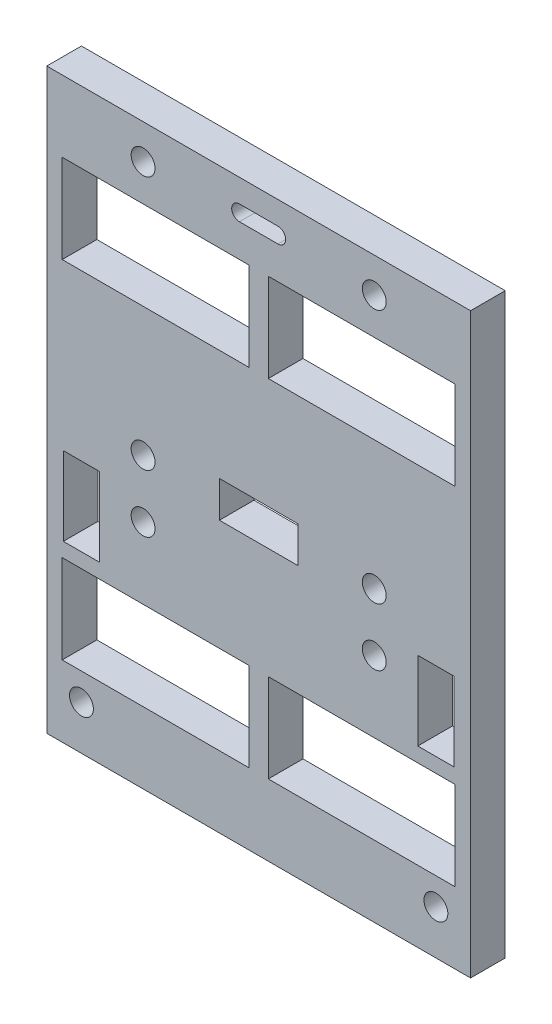
SolidWorks part; units mm, degrees
ref_plane "Front Plane" through (0, 0, 0) normal (0, 0, 1) x (1, 0, 0)
ref_plane "Top Plane" through (0, 0, 0) normal (0, 1, 0) x (1, 0, 0)
ref_plane "Right Plane" through (0, 0, 0) normal (1, 0, 0) x (0, 0, -1)
sketch "Sketch1" plane through (0, 0, 0) normal (0, 0, 1) x (1, 0, 0)
  line L0 (0, -37.5) -> (0, 37.5) construction
  line L1 (-27.5, -37.5) -> (27.5, -37.5)
  line L2 (-27.5, -37.5) -> (-27.5, 37.5)
  line L3 (-27.5, 37.5) -> (27.5, 37.5)
  line L4 (27.5, -37.5) -> (27.5, 37.5)
  line L5 (-27.5, -37.5) -> (27.5, 37.5) construction
  line L6 (-27.5, 37.5) -> (27.5, -37.5) construction
  line L7 (-27.5, 0) -> (27.5, 0) construction
  line L8 (-27.5, 22.5) -> (27.5, 22.5) construction
  line L9 (25.5, 16.75) -> (1.25, 28.25) construction
  line L10 (-25.5, 28.25) -> (-1.25, 28.25)
  line L11 (-25.5, 28.25) -> (-25.5, 16.75)
  line L12 (-25.5, 16.75) -> (-1.25, 16.75)
  line L13 (-1.25, 28.25) -> (-1.25, 16.75)
  line L14 (-25.5, 28.25) -> (-1.25, 16.75) construction
  line L15 (-25.5, 16.75) -> (-1.25, 28.25) construction
  line L16 (25.5, 28.25) -> (1.25, 16.75) construction
  line L17 (1.25, 28.25) -> (1.25, 16.75)
  line L18 (25.5, 16.75) -> (1.25, 16.75)
  line L19 (25.5, 28.25) -> (25.5, 16.75)
  line L20 (25.5, 28.25) -> (1.25, 28.25)
  line L21 (25.5, -28.25) -> (1.25, -16.75) construction
  line L22 (-25.5, -16.75) -> (-1.25, -28.25) construction
  line L23 (-25.5, -28.25) -> (-1.25, -16.75) construction
  line L24 (25.5, -16.75) -> (1.25, -28.25) construction
  line L25 (25.5, -28.25) -> (1.25, -28.25)
  line L26 (25.5, -28.25) -> (25.5, -16.75)
  line L27 (25.5, -16.75) -> (1.25, -16.75)
  line L28 (1.25, -28.25) -> (1.25, -16.75)
  line L29 (-1.25, -28.25) -> (-1.25, -16.75)
  line L30 (-25.5, -16.75) -> (-1.25, -16.75)
  line L31 (-25.5, -28.25) -> (-25.5, -16.75)
  line L32 (-25.5, -28.25) -> (-1.25, -28.25)
  point P0 (0, 0)
  point P12 (-13.375, 22.5)
  point P21 (13.375, 22.5)
  point P30 (13.375, -22.5)
  point P31 (-13.375, -22.5)
  dimension "D1" = 55
  dimension "D2" = 75
  dimension "D3" = 22.5
  dimension "D4" = 24.25
  dimension "D5" = 11.5
  dimension "D6" = 1.25
extrude "Boss-Extrude1" add sketch "Sketch1" along normal blind 4.5
sketch "Sketch2" plane through (0, 0, 4.5) normal (0, 0, 1) x (1, 0, 0)
  line L0 (0, -37.5) -> (0, 37.5) construction
  line L1 (-27.5, -37.5) -> (27.5, -37.5) construction
  line L2 (27.5, 37.5) -> (-27.5, 37.5) construction
  line L3 (-27.5, 0) -> (27.5, 0) construction
  line L4 (-27.5, 37.5) -> (-27.5, -37.5) construction
  line L5 (27.5, -37.5) -> (27.5, 37.5) construction
  line L6 (-15, 0) -> (15, 0) construction
  circle A0 centre (-15, 33) radius 1.55
  circle A1 centre (15, 33) radius 1.55
  circle A2 centre (15, 0) radius 1.55
  circle A3 centre (-15, 0) radius 1.55
  dimension "D1" = 3.1
  dimension "D7" = 3.1
  dimension "D8" = 3.1
  dimension "D2" = 15
  dimension "D3" = 33
  dimension "D4" = 30
  dimension "D5" = 15
  dimension "D6" = 0
extrude "screwHoles" cut sketch "Sketch2" against normal through all
sketch "Sketch3" plane through (0, 0, 4.5) normal (0, 0, 1) x (1, 0, 0)
  line L0 (-27.5, 9) -> (26.0486, 9) construction
  line L1 (-27.5, 37.5) -> (-27.5, -37.5) construction
  line L3 (0, 37.5) -> (0, -37.5) construction
  line L4 (27.5, 37.5) -> (-27.5, 37.5) construction
  line L5 (-27.5, -37.5) -> (27.5, -37.5) construction
  line L6 (19.1, 6.65) -> (8.9, 11.35) construction
  line L7 (-19.1, 11.35) -> (-8.9, 11.35)
  line L8 (-19.1, 11.35) -> (-19.1, 6.65)
  line L9 (-19.1, 6.65) -> (-8.9, 6.65)
  line L10 (-8.9, 11.35) -> (-8.9, 6.65)
  line L11 (-19.1, 11.35) -> (-8.9, 6.65) construction
  line L12 (-19.1, 6.65) -> (-8.9, 11.35) construction
  line L13 (19.1, 11.35) -> (8.9, 6.65) construction
  line L14 (8.9, 11.35) -> (8.9, 6.65)
  line L15 (19.1, 6.65) -> (8.9, 6.65)
  line L16 (19.1, 11.35) -> (19.1, 6.65)
  line L17 (19.1, 11.35) -> (8.9, 11.35)
  line L18 (-27.5, 37.5) -> (-27.5, -37.5) construction
  point P2 (-27.5, 0)
  point P12 (-14, 9)
  point P21 (14, 9)
  dimension "D1" = 10.2
  dimension "D2" = 4.7
  dimension "D3" = 14
  dimension "D4" = 9
extrude "BeltClamp" [suppressed] cut sketch "Sketch3" against normal through all
sketch "Sketch4" plane through (0, 0, 4.5) normal (0, 0, 1) x (1, 0, 0)
  line L0 (-27.5, 0) -> (27.5, 0) construction
  line L1 (-27.5, 37.5) -> (-27.5, -37.5) construction
  line L2 (27.5, -37.5) -> (27.5, 37.5) construction
  line L4 (-5.1, 2.35) -> (5.1, 2.35)
  line L5 (-5.1, 2.35) -> (-5.1, -2.35)
  line L6 (-5.1, -2.35) -> (5.1, -2.35)
  line L7 (5.1, 2.35) -> (5.1, -2.35)
  line L8 (-5.1, 2.35) -> (5.1, -2.35) construction
  line L9 (-5.1, -2.35) -> (5.1, 2.35) construction
  circle A0 centre (-15, 0) radius 1.55 construction
  point P6 (0, 0)
  dimension "D1" = 10.2
  dimension "D2" = 4.7
  dimension "D3" = 0
extrude "mountingPlateTab" cut sketch "Sketch4" against normal through all
sketch "Sketch5" plane through (0, 0, 4.5) normal (0, 0, 1) x (1, 0, 0)
  line L0 (-27.5, -9.75) -> (27.5, -9.75) construction
  line L1 (-27.5, 37.5) -> (-27.5, -37.5) construction
  line L2 (27.5, -37.5) -> (27.5, 37.5) construction
  line L3 (5.1, -2.35) -> (5.1, 2.35) construction
  line L4 (0, -37.5) -> (0, 37.5) construction
  line L5 (-27.5, -37.5) -> (27.5, -37.5) construction
  line L6 (27.5, 37.5) -> (-27.5, 37.5) construction
  line L7 (-20.65, -14.85) -> (-25.35, -4.65) construction
  line L8 (20.65, -4.65) -> (25.35, -4.65)
  line L9 (20.65, -4.65) -> (20.65, -14.85)
  line L10 (20.65, -14.85) -> (25.35, -14.85)
  line L11 (25.35, -4.65) -> (25.35, -14.85)
  line L12 (20.65, -4.65) -> (25.35, -14.85) construction
  line L13 (20.65, -14.85) -> (25.35, -4.65) construction
  line L14 (-20.65, -4.65) -> (-25.35, -14.85) construction
  line L15 (-25.35, -4.65) -> (-25.35, -14.85)
  line L16 (-20.65, -14.85) -> (-25.35, -14.85)
  line L17 (-20.65, -4.65) -> (-20.65, -14.85)
  line L18 (-20.65, -4.65) -> (-25.35, -4.65)
  line L19 (23, -9.75) -> (23, -37.5) construction
  line L20 (-23, -9.75) -> (-23, -37.5) construction
  circle A0 centre (23, -31.75) radius 1.55
  circle A1 centre (-23, -31.75) radius 1.55
  point P6 (5.1, 0)
  point P15 (23, -9.75)
  point P24 (-23, -9.75)
  dimension "D5" = 3.1
  dimension "D1" = 9.75
  dimension "D2" = 10.2
  dimension "D3" = 4.7
  dimension "D4" = 23
  dimension "D6" = 22
extrude "BraceTabs" cut sketch "Sketch5" against normal through all
sketch "Sketch6" plane through (0, 0, 4.5) normal (0, 0, 1) x (1, 0, 0)
  line L0 (-25.35, -9.75) -> (25.35, -9.75) construction
  line L1 (-25.35, -4.65) -> (-25.35, -14.85) construction
  line L2 (25.35, -14.85) -> (25.35, -4.65) construction
  line L3 (0, -2.35) -> (0, -37.5) construction
  line L4 (-5.1, -2.35) -> (5.1, -2.35) construction
  line L5 (-27.5, -37.5) -> (27.5, -37.5) construction
  line L6 (23, -14.85) -> (23, -4.65) construction
  line L7 (20.65, -14.85) -> (25.35, -14.85) construction
  line L8 (25.35, -4.65) -> (20.65, -4.65) construction
  line L9 (20.65, -4.65) -> (20.65, -14.85) construction
  line L10 (19.65, -15.85) -> (26.35, -15.85)
  line L11 (19.65, -15.85) -> (19.65, -3.65)
  line L12 (19.65, -3.65) -> (26.35, -3.65)
  line L13 (26.35, -15.85) -> (26.35, -3.65)
  line L14 (19.65, -15.85) -> (26.35, -3.65) construction
  line L15 (19.65, -3.65) -> (26.35, -15.85) construction
  line L16 (-19.65, -3.65) -> (-26.35, -15.85) construction
  line L17 (-19.65, -15.85) -> (-26.35, -3.65) construction
  line L18 (-23, -14.85) -> (-23, -4.65) construction
  line L19 (-26.35, -15.85) -> (-26.35, -3.65)
  line L20 (-19.65, -3.65) -> (-26.35, -3.65)
  line L21 (-19.65, -15.85) -> (-19.65, -3.65)
  line L22 (-19.65, -15.85) -> (-26.35, -15.85)
  circle A0 centre (23, -9.75) radius 1.55
  circle A1 centre (-23, -9.75) radius 1.55
  point P18 (23, -9.75)
  dimension "D3" = 3.1
  dimension "D1" = 1
  dimension "D2" = 1
extrude "FrontToRear1" [suppressed] add sketch "Sketch6" against normal up to surface (4.5 mm away) up to face at (-24.55, -31.75, 0)
sketch "Sketch7" plane through (0, 0, 4.5) normal (0, 0, 1) x (1, 0, 0)
  line L0 (5.1, 2.35) -> (-5.1, 2.35) construction
  line L1 (-20, -3.35) -> (20, -3.35)
  line L2 (-20, -3.35) -> (-20, 3.35)
  line L3 (-20, 3.35) -> (20, 3.35)
  line L4 (20, -3.35) -> (20, 3.35)
  line L5 (-20, -3.35) -> (20, 3.35) construction
  line L6 (-20, 3.35) -> (20, -3.35) construction
  circle A0 centre (15, 0) radius 1.55 construction
  point P0 (0, 0)
  dimension "D1" = 1
  dimension "D2" = 5
extrude "FrontToRear2" [suppressed] add sketch "Sketch7" against normal through all
sketch "Sketch8" plane through (0, 0, 4.5) normal (0, 0, 1) x (1, 0, 0)
  line L0 (-27.5, -7.5) -> (27.5, -7.5) construction
  line L1 (-27.5, 37.5) -> (-27.5, -37.5) construction
  line L2 (27.5, -37.5) -> (27.5, 37.5) construction
  line L3 (0, -37.5) -> (0, 0) construction
  line L4 (-27.5, -37.5) -> (27.5, -37.5) construction
  circle A0 centre (-15, -7.5) radius 1.55
  circle A1 centre (15, -7.5) radius 1.55
  dimension "D2" = 3.1
  dimension "D1" = 7.5
  dimension "D3" = 15
extrude "ExpansionScrewholes" cut sketch "Sketch8" against normal through all
sketch "Sketch12" plane through (0, 0, 4.5) normal (0, 0, 1) x (1, 0, 0)
  line L0 (0, 37.5) -> (0, 0) construction
  line L1 (27.5, 37.5) -> (-27.5, 37.5) construction
  line L2 (-2.5, 33.5) -> (2.5, 33.5) construction
  line L3 (-2.5, 34.5) -> (2.5, 34.5)
  line L4 (-2.5, 32.5) -> (2.5, 32.5)
  arc A0 (-2.5, 34.5) -> (-2.5, 32.5) centre (-2.5, 33.5) ccw
  arc A1 (2.5, 32.5) -> (2.5, 34.5) centre (2.5, 33.5) ccw
  point P7 (0, 33.5)
  dimension "D1" = 3
  dimension "D2" = 2
  dimension "D3" = 5
extrude "CableTieSlot" cut sketch "Sketch12" against normal through all
sketch "Sketch11" [suppressed] plane through (0, 0, 4.5) normal (0, 0, 1) x (1, 0, 0)
  line L0 (13.5615, -8.85) -> (27.5, -8.85) construction
  line L1 (27.5, -37.5) -> (27.5, 37.5) construction
  line L2 (0, 2.35) -> (0, -2.35) construction
  line L3 (36.5, -14.85) -> (18.5, -14.85)
  line L4 (36.5, -14.85) -> (36.5, -2.85)
  line L5 (36.5, -2.85) -> (18.5, -2.85)
  line L6 (18.5, -14.85) -> (18.5, -2.85)
  line L7 (36.5, -14.85) -> (18.5, -2.85) construction
  line L8 (36.5, -2.85) -> (18.5, -14.85) construction
  line L9 (5.1, 2.35) -> (-5.1, 2.35) construction
  line L10 (-5.1, -2.35) -> (5.1, -2.35) construction
  line L11 (-36.5, -2.85) -> (-18.5, -14.85) construction
  line L12 (-36.5, -14.85) -> (-18.5, -2.85) construction
  line L13 (-18.5, -14.85) -> (-18.5, -2.85)
  line L14 (-36.5, -2.85) -> (-18.5, -2.85)
  line L15 (-36.5, -14.85) -> (-36.5, -2.85)
  line L16 (-36.5, -14.85) -> (-18.5, -14.85)
  line L17 (36.5, -2.85) -> (18.5, -14.85) construction
  line L18 (20.65, -14.85) -> (25.35, -14.85) construction
  dimension "D1" = 9
  dimension "D2" = 12
  dimension "D3" = 0
extrude "Cut-Extrude2" [suppressed] cut sketch "Sketch11" against normal through all
sketch "Sketch10" plane through (0, 0, 4.5) normal (0, 0, 1) x (1, 0, 0)
  line L0 (4.7446, 1) -> (27.5, 1) construction
  line L1 (-5.1, 0) -> (5.1, 0) construction
  line L2 (27.5, -37.5) -> (27.5, 37.5) construction
  line L3 (0, 2.35) -> (0, -2.35) construction
  line L4 (36.5, 4) -> (18.5, 4)
  line L5 (36.5, 4) -> (36.5, -2)
  line L6 (36.5, -2) -> (18.5, -2)
  line L7 (18.5, 4) -> (18.5, -2)
  line L8 (36.5, 4) -> (18.5, -2) construction
  line L9 (36.5, -2) -> (18.5, 4) construction
  line L10 (5.1, 2.35) -> (-5.1, 2.35) construction
  line L11 (-5.1, -2.35) -> (5.1, -2.35) construction
  line L12 (-36.5, -2) -> (-18.5, 4) construction
  line L13 (-36.5, 4) -> (-18.5, -2) construction
  line L14 (-4.7446, 1) -> (-27.5, 1) construction
  line L15 (-18.5, 4) -> (-18.5, -2)
  line L16 (-36.5, -2) -> (-18.5, -2)
  line L17 (-36.5, 4) -> (-36.5, -2)
  line L18 (-36.5, 4) -> (-18.5, 4)
  line L19 (36.5, -2) -> (18.5, 4) construction
  line L20 (-5.1, 2.35) -> (-5.1, -2.35) construction
  line L21 (5.1, -2.35) -> (5.1, 2.35) construction
  dimension "D1" = 6
  dimension "D2" = 9
  dimension "D3" = 1
extrude "CableTieSlots" [suppressed] cut sketch "Sketch10" against normal through all
sketch "Sketch9" [suppressed] plane through (0, 0, 4.5) normal (0, 0, 1) x (1, 0, 0)
  line L0 (-27.5, -37.5) -> (27.5, -37.5) construction
  line L5 (-9, -42.5) -> (9, -42.5)
  line L6 (-9, -42.5) -> (-9, -34.5)
  line L7 (-7, -32.5) -> (7, -32.5)
  line L8 (9, -42.5) -> (9, -34.5)
  line L9 (-9, -42.5) -> (9, -32.5) construction
  line L10 (-9, -32.5) -> (9, -42.5) construction
  arc A0 (7, -32.5) -> (9, -34.5) centre (7, -34.5) cw
  arc A1 (-9, -34.5) -> (-7, -32.5) centre (-7, -34.5) cw
  point P9 (0, -37.5)
  line M42 (-27.5, -37.5) -> (27.5, -37.5)
  dimension "D3" = 2
  dimension "D1" = 18
  dimension "D2" = 5
extrude "RearFanSlot" [suppressed] cut sketch "Sketch9" against normal through all contours A1 L6 L8 A0 L7 M42 | L5 L8 L6 M42
equation "\"X-ROD-SPACING\"=45"
equation "\"Y-ROD-SPACING\"=75"
equation "\"Z-ROD-SPACING\"=17.5"
equation "\"Y-BED-OFFSET\"=2"
equation "\"Y-BED-ROD-INSET\"=3.5"
equation "\"Y-BED-SCREW-SPACING\"=209"
equation "\"Y-BED-SCREW-CUTOUT-SLOT-HEIGHT\"=2"
equation "\"T-SLOT-NUT-FILLET-RADIUS\"=0.25"
equation "\"T-SLOT-SCREW-SHAFT-RADIUS\"=1.75"
equation "\"T-SLOT-SCREW-SHAFT-CUTOUT-LENGTH\"=10.5"
equation "\"T-SLOT-NUT-DEPTH\"=4.2"
equation "\"T-SLOT-NUT-WIDTH\"=3"
equation "\"T-SLOT-NUT-END-DISTANCE\"=8"
equation "\"ACRYLIC-THICKNESS\"=10"
equation "\"ACRYLIC-THICKNESS2\"=4.5"
equation "\"ACRYLIC-TAB-CUTOUT-SIZE\"=\"ACRYLIC-THICKNESS\"+\"ACRYLIC-TAB-TOLERANCE\"*2"
equation "\"ACRYLIC-TAB-WIDTH\"=\"ACRYLIC-THICKNESS\""
equation "\"ACRYLIC-M3-HOLE\"=3.1"
equation "\"SMOOTHROD-CAP-SCREW-DISTANCE\"=20"
equation "\"FRAME-WIDTH-INNER\"=370"
equation "\"NEMA17-HOLE-SPACING\"=31"
equation "\"NEMA17-CENTRAL-CUTOUT\"=22.5"
equation "\"Z-BRACKET-REACH\"=55"
equation "\"Z-ROD-INSET\"=16"
equation "\"TOP-BRACKET-SPACING\"=40"
equation "\"SMOOTHROD-X-LENGTH\"=350"
equation "\"SMOOTHROD-Y-LENGTH\"=350"
equation "\"SMOOTHROD-Z-LENGTH\"=350"
equation "\"SMOOTHROD-TIGHTENING-HEADROOM\"=.25"
equation "\"LEADSCREW-Z-LENGTH\"=300"
equation "\"SCREW-LENGTH-FRAME\"=\"ACRYLIC-THICKNESS\" + 10"
equation "\"SCREW-LENGTH-MOTOR\"=\"ACRYLIC-THICKNESS\" + 5"
equation "\"SCREW-HEAD-RADIUS\"=6"
equation "\"PRINTED-X-SMOOTHROD-DIAMETER\"=8.2"
equation "\"PRINTED-X-SMOOTHROD-CUTOUT\"=10"
equation "\"PRINTED-X-BASE-HEIGHT\"=10"
equation "\"PRINTED-LM8UU-CUTOUT-SIZE\"=15.25"
equation "\"PRINTED-LM8UU-CUTOUT-LENGTH\"=24.5"
equation "\"PRINTED-X-IDLER-HEIGHT\"=16"
equation "\"PSU-MOUNTING-WIDTH\"=95"
equation "\"PSU-MOUNTING-HEIGHT\"=177"
equation "\"Y-BELT-TO-ROD-DISTANCE\"=20"
equation "\"SPOOL-HOLDER-ROD-SPACING\"=150"
equation "\"D3@Sketch1\"=\"X-ROD-SPACING\"/2"
equation "\"D4@Sketch1\"=\"ACRYLIC-X-CARRIAGE-LM8UU-CUTOUT-WIDTH\""
equation "\"D1@Boss-Extrude1\"=\"ACRYLIC-THICKNESS2\""
equation "\"D1@Sketch2\"=\"ACRYLIC-M3-HOLE\""
equation "\"D1@Sketch3\"=\"ACRYLIC-TAB-CUTOUT-SIZE\""
equation "\"D2@Sketch3\"=\"ACRYLIC-THICKNESS2\"+\"ACRYLIC-TAB-TOLERANCE\"*2"
equation "\"ACRYLIC-X-CARRIAGE-WIDTH\"=55"
equation "\"ACRYLIC-X-CARRIAGE-HEIGHT\"=75"
equation "\"D1@Sketch1\"=\"ACRYLIC-X-CARRIAGE-WIDTH\""
equation "\"D2@Sketch1\"=\"ACRYLIC-X-CARRIAGE-HEIGHT\""
equation "\"ACRYLIC-X-CARRIAGE-CENTER-TAB-SPACING\"=14"
equation "\"D3@Sketch3\"=\"ACRYLIC-X-CARRIAGE-CENTER-TAB-SPACING\""
equation "\"SCREW-LENGTH-EXTRUDER\"=28"
equation "\"ACRYLIC-X-CARRIAGE-SCREW-SPACING-X\"=15"
equation "\"ACRYLIC-X-CARRIAGE-SCREW-SPACING-Y\"=33"
equation "\"D2@Sketch2\"=\"ACRYLIC-X-CARRIAGE-SCREW-SPACING-X\""
equation "\"D3@Sketch2\"=\"ACRYLIC-X-CARRIAGE-SCREW-SPACING-Y\""
equation "\"D1@Sketch4\"=\"ACRYLIC-TAB-CUTOUT-SIZE\""
equation "\"D2@Sketch4\"=\"ACRYLIC-THICKNESS2\"+\"ACRYLIC-TAB-TOLERANCE\"*2"
equation "\"D2@Sketch5\"=\"ACRYLIC-TAB-CUTOUT-SIZE\""
equation "\"D3@Sketch5\"=\"ACRYLIC-THICKNESS2\"+\"ACRYLIC-TAB-TOLERANCE\"*2"
equation "\"ACRYLIC-X-CARRIAGE-EXTRUDER-SHELF-DEPTH\"=\"ACRYLIC-X-CARRIAGE-EXTRUDER-OFFSET\" + 28"
equation "\"ACRYLIC-X-CARRIAGE-EXTRUDER-BRACE-SPACING\"=23"
equation "\"D4@Sketch5\"=\"ACRYLIC-X-CARRIAGE-EXTRUDER-BRACE-SPACING\""
equation "\"D1@Sketch5\"=\"ACRYLIC-THICKNESS2\"/2 + 7.5"
equation "\"D4@Sketch2\"=\"ACRYLIC-X-CARRIAGE-SCREW-SPACING-X\"*2"
equation "\"D5@Sketch2\"=\"ACRYLIC-X-CARRIAGE-SCREW-SPACING-X\""
equation "\"D7@Sketch2\"=\"ACRYLIC-M3-HOLE\""
equation "\"D8@Sketch2\"=\"ACRYLIC-M3-HOLE\""
equation "\"ACRYLIC-X-CARRIAGE-LM8UU-CUTOUT-WIDTH\"=24.25"
equation "\"ACRYLIC-TAB-TOLERANCE\"=.1"
equation "\"ACRYLIC-X-CARRIAGE-EXTRUDER-OFFSET\"=26"
equation "\"ACRYLIC-X-CARRIAGE-EXTRUDER-ANGLE\"=90"
equation "\"ACRYLIC-X-CARRIAGE-EXTRUDER-BRACE-TAB-OFFSET\"=20"
equation "\"ACRYLIC-X-CARRIAGE-EXTRUDER-BRACE-HEIGHT\"=35"
equation "\"ACRYLIC-X-CARRIAGE-EXTRUDER-BRACE-SCREW-SPACING\"=22"
equation "\"D5@Sketch5\"=\"ACRYLIC-M3-HOLE\""
equation "\"D3@Sketch6\"=\"ACRYLIC-M3-HOLE\""
equation "\"ACRYLIC-X-CARRIAGE-LM8UU-CUTOUT-HEIGHT\"=11.5"
equation "\"ACRYLIC-X-CARRIAGE-DUAL-WIDTH-MULTIPLIER\"=1.65"
equation "\"ACRYLIC-X-CARRIAGE-DUAL-HOTEND-SPACING\"=42"
equation "\"ACRYLIC-X-CARRIAGE-DUAL-WIDTH\"=103"
equation "\"ACRYLIC-X-CARRIAGE-DUAL-HOTEND-SEPARATION\"=35"
equation "\"ACRYLIC-X-CARRIAGE-DUAL-MOUNT-PLATE-DEPTH\"=76"
equation "\"ACRYLIC-X-CARRIAGE-DUAL-MOUNT-BRACE-WIDTH\"=45"
equation "\"ACRYLIC-X-CARRIAGE-DUAL-MOUNT-SCREW-WIDTH\"=40"
equation "\"D5@Sketch1\"=\"ACRYLIC-X-CARRIAGE-LM8UU-CUTOUT-HEIGHT\""
equation "\"D2@Sketch8\"=\"ACRYLIC-M3-HOLE\""
